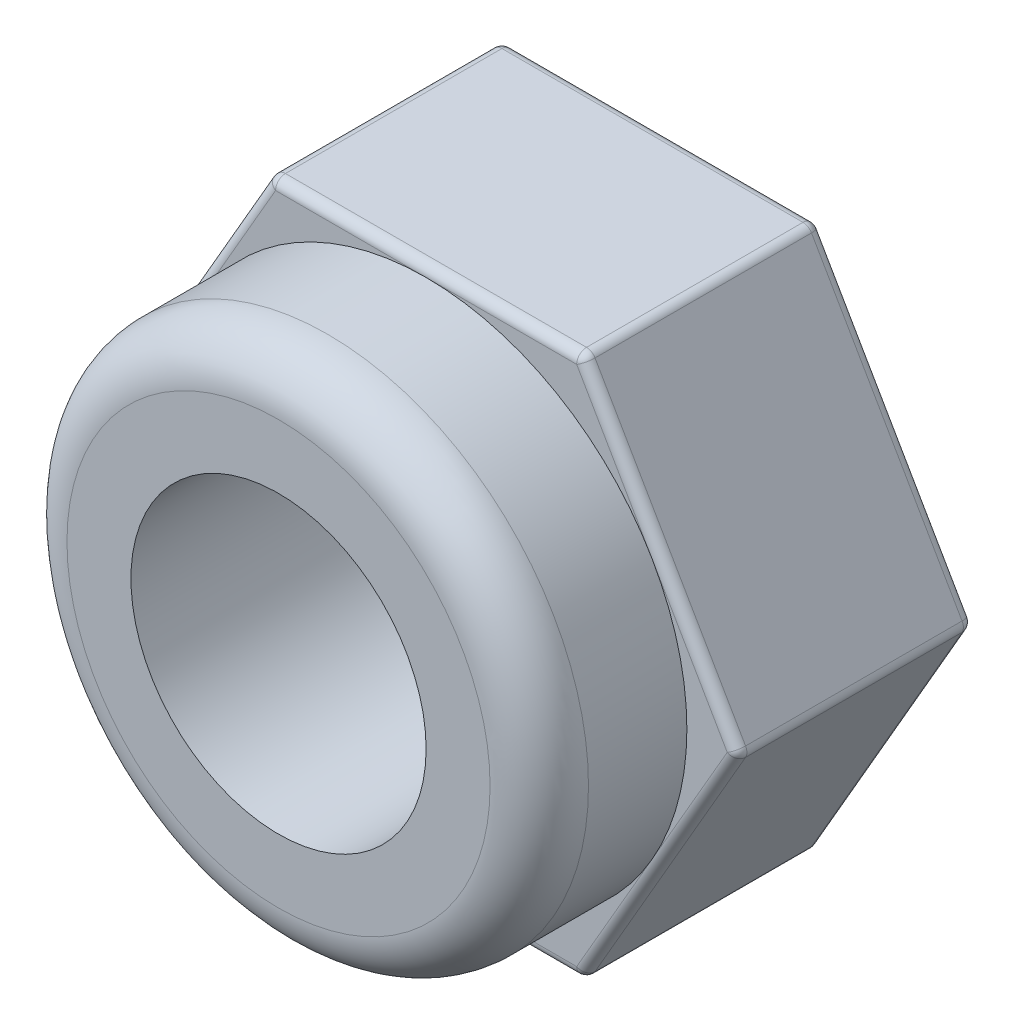
SolidWorks part; units mm, degrees
material "合金钢"
ref_plane "前视基准面" through (0, 0, 0) normal (0, 0, 1) x (1, 0, 0)
ref_plane "上视基准面" through (0, 0, 0) normal (0, 1, 0) x (1, 0, 0)
ref_plane "右视基准面" through (0, 0, 0) normal (1, 0, 0) x (0, 0, -1)
sketch "草图1" plane through (0, 0, 0) normal (0, 0, 1) x (1, 0, 0)
  line L1 (3.1754, 0) -> (1.5877, 2.75)
  line L2 (1.5877, 2.75) -> (-1.5877, 2.75)
  line L3 (-1.5877, 2.75) -> (-3.1754, 0)
  line L4 (-3.1754, 0) -> (-1.5877, -2.75)
  line L5 (-1.5877, -2.75) -> (1.5877, -2.75)
  line L6 (1.5877, -2.75) -> (3.1754, 0)
  circle A0 centre (0, 0) radius 2.75 construction
  dimension "D1" = 5.5
extrude "凸台-拉伸1" add sketch "草图1" along normal blind 2.4
sketch "草图2" plane through (0, 0, 2.4) normal (0, 0, 1) x (1, 0, 0)
  line L0 (3.1754, 0) -> (-3.1754, 0) construction
  circle A0 centre (0, 0) radius 2.65
  dimension "D1" = 5.3
extrude "凸台-拉伸2" add sketch "草图2" along normal blind 3.9 from surface starting at face at (0, 0, 0)
fillet "圆角1" radius 0.5 1 edges at (2.65, 0, 3.9)
fillet "圆角2" radius 0.1 18 edges at (2.3816, 1.375, 2.4) (2.3816, 1.375, 0) (2.3816, -1.375, 2.4) (3.1754, 0, 1.2) (2.3816, -1.375, 0) (0, -2.75, 2.4) (1.5877, -2.75, 1.2) (0, -2.75, 0) (-2.3816, -1.375, 2.4) (-1.5877, -2.75, 1.2) (-2.3816, -1.375, 0) (-2.3816, 1.375, 2.4) (-3.1754, 0, 1.2) (-2.3816, 1.375, 0) (1.5877, 2.75, 1.2) (0, 2.75, 2.4) (-1.5877, 2.75, 1.2) (0, 2.75, 0)
sketch "草图3" plane through (0, 0, 3.9) normal (0, 0, 1) x (1, 0, 0)
  circle A0 centre (0, 0) radius 1.5
  dimension "D1" = 3
extrude "切除-拉伸1" cut sketch "草图3" against normal through all
